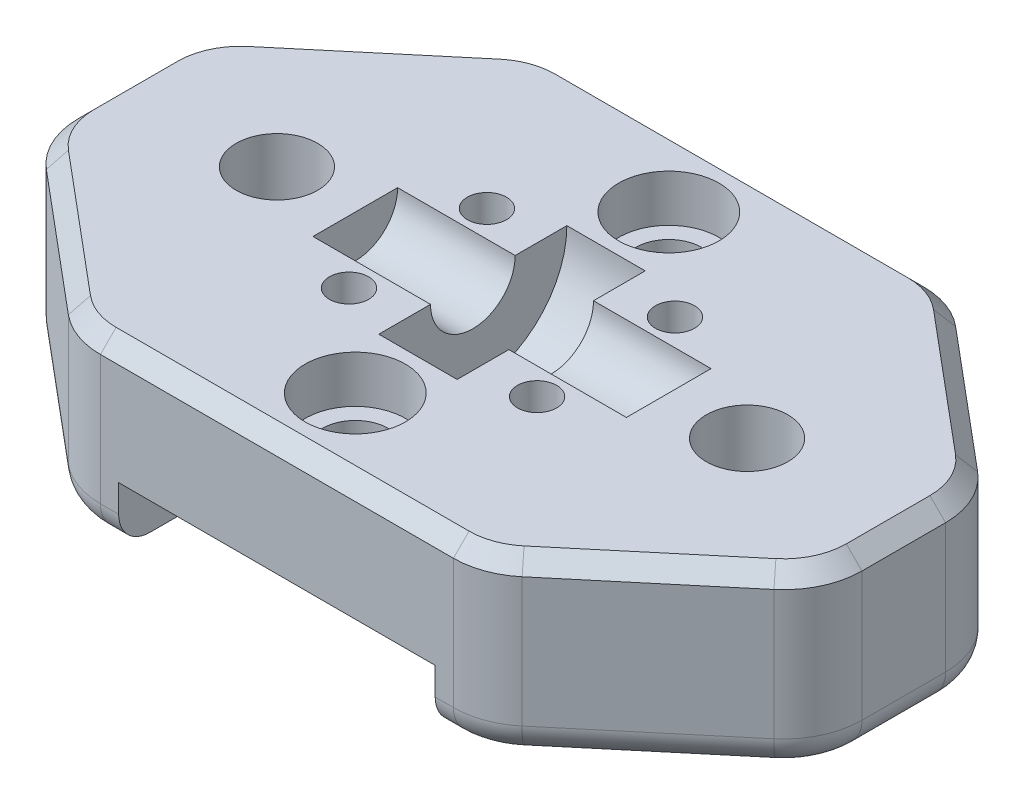
SolidWorks part; units mm, degrees
ref_plane "Front Plane" through (0, 0, 0) normal (0, 0, 1) x (1, 0, 0)
ref_plane "Top Plane" through (0, 0, 0) normal (0, 1, 0) x (1, 0, 0)
ref_plane "Right Plane" through (0, 0, 0) normal (1, 0, 0) x (0, 0, -1)
sketch "Sketch1" plane through (0, 0, 0) normal (0, 1, 0) x (1, 0, 0)
  line L0 (14.3035, 0) -> (-14.3035, 0)
  line L1 (-18.3852, 1.4856) -> (-29.4817, 10.7967)
  line L2 (-31.75, 15.6611) -> (-31.75, 22.4389)
  line L3 (-31.75, 19.05) -> (0, 19.05) construction
  line L4 (0, 19.05) -> (0, 0) construction
  line L5 (18.3852, 1.4856) -> (29.4817, 10.7967)
  line L6 (31.75, 15.6611) -> (31.75, 22.4389)
  line L7 (-18.3852, 36.6144) -> (-29.4817, 27.3033)
  line L8 (14.3035, 38.1) -> (-14.3035, 38.1)
  line L9 (18.3852, 36.6144) -> (29.4817, 27.3033)
  arc A0 (-29.4817, 10.7967) -> (-31.75, 15.6611) centre (-25.4, 15.6611) cw
  arc A1 (-18.3852, 1.4856) -> (-14.3035, 0) centre (-14.3035, 6.35) ccw
  arc A2 (18.3852, 1.4856) -> (14.3035, 0) centre (14.3035, 6.35) cw
  arc A3 (29.4817, 10.7967) -> (31.75, 15.6611) centre (25.4, 15.6611) ccw
  arc A4 (-29.4817, 27.3033) -> (-31.75, 22.4389) centre (-25.4, 22.4389) ccw
  arc A5 (-18.3852, 36.6144) -> (-14.3035, 38.1) centre (-14.3035, 31.75) cw
  arc A6 (18.3852, 36.6144) -> (14.3035, 38.1) centre (14.3035, 31.75) ccw
  arc A7 (29.4817, 27.3033) -> (31.75, 22.4389) centre (25.4, 22.4389) cw
  point P9 (-31.75, 12.7)
  point P31 (31.75, 19.05)
  dimension "D5" = 6.35
  dimension "D6" = 6.35
  dimension "D1" = 19.05
  dimension "D2" = 6.35
  dimension "D3" = 31.75
  dimension "D4" = 140
extrude "Boss-Extrude2" add sketch "Sketch1" along normal blind 14.2875
sketch "Sketch2" plane through (0, 14.2875, 0) normal (0, 1, 0) x (1, 0, 0)
  line L0 (-14.3035, 0) -> (14.3035, 0) construction
  line L2 (14.3035, 38.1) -> (-14.3035, 38.1) construction
  line L3 (0, 38.1) -> (0, 0) construction
  circle A0 centre (-19.05, 19.05) radius 3.302
  circle A3 centre (19.05, 19.05) radius 3.302
  circle A8 centre (7.62, 24.638) radius 1.5875
  circle A9 centre (7.62, 13.462) radius 1.5875
  circle A10 centre (-7.62, 13.462) radius 1.5875
  circle A11 centre (-7.62, 24.638) radius 1.5875
  circle A12 centre (0, 31.75) radius 2.667
  circle A13 centre (0, 6.35) radius 2.667
  point P4 (0, 0)
  dimension "D2" = 6.604
  dimension "D7" = 7.62
  dimension "D8" = 3.175
  dimension "D10" = 5.588
  dimension "D4" = 5.334
  dimension "D1" = 19.05
  dimension "D3" = 19.05
  dimension "D5" = 6.35
  dimension "D6" = 6.35
  dimension "D9" = 5.588
  dimension "D11" = 7.62
  dimension "D12" = 25.4
extrude "Cut-Extrude1" cut sketch "Sketch2" against normal through all
sketch "Sketch3" plane through (-31.75, 0, 0) normal (-1, 0, 0) x (0, 0, 1)
  line L0 (-22.4389, 14.2875) -> (-15.6611, 14.2875) construction
  circle A0 centre (-19.05, 14.2875) radius 3.429
  dimension "D1" = 6.858
extrude "Cut-Extrude3" cut sketch "Sketch3" against normal blind 25.4 from offset 19.05 offset against normal yes
sketch "Sketch4" plane through (-31.75, 0, 0) normal (-1, 0, 0) x (0, 0, 1)
  line L0 (-22.4389, 14.2875) -> (-15.6611, 14.2875) construction
  line L1 (-26.67, 14.2875) -> (-11.43, 14.2875)
  arc A0 (-26.67, 14.2875) -> (-11.43, 14.2875) centre (-19.05, 14.2875) ccw
  dimension "D1" = 7.62
extrude "Cut-Extrude4" cut sketch "Sketch4" against normal blind 6.35 from offset 28.575 offset against normal yes
sketch "Sketch5" plane through (0, 0, -38.1) normal (0, 0, -1) x (-1, 0, 0)
  line L0 (-14.3035, 0) -> (14.3035, 0) construction
  line L1 (12.827, 0) -> (-12.827, 0)
  line L2 (12.827, 0) -> (12.827, 4.7625)
  line L3 (12.827, 4.7625) -> (-12.827, 4.7625)
  line L4 (-12.827, 0) -> (-12.827, 4.7625)
  line L5 (-14.3035, 14.2875) -> (14.3035, 14.2875) construction
  point P10 (0, 14.2875)
  dimension "D1" = 25.654
  dimension "D2" = 4.7625
  dimension "D3" = 12.827
extrude "Cut-Extrude5" cut sketch "Sketch5" against normal through all
sketch "Sketch6" plane through (0, 0, 0) normal (0, -1, 0) x (1, 0, 0)
  line L1 (13.208, -22.4229) -> (19.05, -25.7958)
  line L2 (19.05, -25.7958) -> (24.892, -22.4229)
  line L3 (24.892, -22.4229) -> (24.892, -15.6771)
  line L4 (24.892, -15.6771) -> (19.05, -12.3042)
  line L5 (19.05, -12.3042) -> (13.208, -15.6771)
  line L6 (13.208, -15.6771) -> (13.208, -22.4229)
  line L7 (-19.05, -25.7958) -> (-13.208, -22.4229)
  line L8 (-13.208, -22.4229) -> (-13.208, -15.6771)
  line L9 (-13.208, -15.6771) -> (-19.05, -12.3042)
  line L10 (-19.05, -12.3042) -> (-24.892, -15.6771)
  line L11 (-24.892, -15.6771) -> (-24.892, -22.4229)
  line L12 (-24.892, -22.4229) -> (-19.05, -25.7958)
  circle A0 centre (19.05, -19.05) radius 5.842 construction
  circle A1 centre (-19.05, -19.05) radius 5.842 construction
  dimension "D1" = 11.684
extrude "Cut-Extrude6" cut sketch "Sketch6" against normal blind 6.35
sketch "Sketch9" plane through (0, 4.7625, 0) normal (0, -1, 0) x (1, 0, 0)
  line L0 (9.2075, -13.462) -> (9.2075, -24.638)
  line L1 (6.0325, -13.462) -> (6.0325, -24.638)
  line L2 (-6.0325, -24.638) -> (-6.0325, -13.462)
  line L3 (-9.2075, -24.638) -> (-9.2075, -13.462)
  circle A0 centre (7.62, -13.462) radius 1.5875 construction
  circle A1 centre (7.62, -24.638) radius 1.5875 construction
  circle A2 centre (-7.62, -24.638) radius 1.5875 construction
  circle A3 centre (-7.62, -13.462) radius 1.5875 construction
  arc A4 (9.2075, -24.638) -> (6.0325, -24.638) centre (7.62, -24.638) cw
  arc A5 (-6.0325, -24.638) -> (-9.2075, -24.638) centre (-7.62, -24.638) cw
  arc A6 (-9.2075, -13.462) -> (-6.0325, -13.462) centre (-7.62, -13.462) cw
  arc A7 (6.0325, -13.462) -> (9.2075, -13.462) centre (7.62, -13.462) cw
extrude "Cut-Extrude9" cut sketch "Sketch9" against normal blind 3.175
chamfer "Chamfer2" distance 2.54 angle 45 4 edges at (-7.62, 7.9375, -15.0495) (-7.62, 7.9375, -23.0505) (7.62, 7.9375, -15.0495) (7.62, 7.9375, -23.0505)
sketch "Sketch10" plane through (0, 14.2875, 0) normal (0, 1, 0) x (1, 0, 0)
  circle A0 centre (0, 6.35) radius 4.064
  circle A1 centre (0, 31.7584) radius 4.064
  dimension "D1" = 8.128
extrude "Cut-Extrude10" cut sketch "Sketch10" against normal blind 3.81
fillet "Fillet1" radius 2.54 18 edges at (-31.1551, 0, -25.1226) (-31.75, 0, -19.05) (-31.1551, 0, -12.9774) (-23.9335, 0, -6.1411) (-16.4753, 0, -0.383) (-13.5653, 0, 0) (-23.9335, 0, -31.9589) (-16.4753, 0, -37.717) (-13.5653, 0, -38.1) (13.5653, 0, 0) (16.4753, 0, -0.383) (23.9335, 0, -6.1411) (31.1551, 0, -12.9774) (31.75, 0, -19.05) (31.1551, 0, -25.1226) (23.9335, 0, -31.9589) (16.4753, 0, -37.717) (13.5653, 0, -38.1)
fillet "Fillet2" radius 1.27 8 edges at (-7.62, 4.7625, -26.2255) (-9.2075, 4.7625, -19.05) (-7.62, 4.7625, -11.8745) (-6.0325, 4.7625, -19.05) (7.62, 4.7625, -11.8745) (9.2075, 4.7625, -19.05) (7.62, 4.7625, -26.2255) (6.0325, 4.7625, -19.05)
chamfer "Chamfer3" distance 1.27 angle 45 16 edges at (16.4753, 14.2875, -37.717) (0, 14.2875, -38.1) (-16.4753, 14.2875, -37.717) (-23.9335, 14.2875, -31.9589) (-31.1551, 14.2875, -25.1226) (-31.75, 14.2875, -19.05) (-31.1551, 14.2875, -12.9774) (-23.9335, 14.2875, -6.1411) (-16.4753, 14.2875, -0.383) (0, 14.2875, 0) (16.4753, 14.2875, -0.383) (23.9335, 14.2875, -6.1411) (31.1551, 14.2875, -12.9774) (31.75, 14.2875, -19.05) (31.1551, 14.2875, -25.1226) (23.9335, 14.2875, -31.9589)
